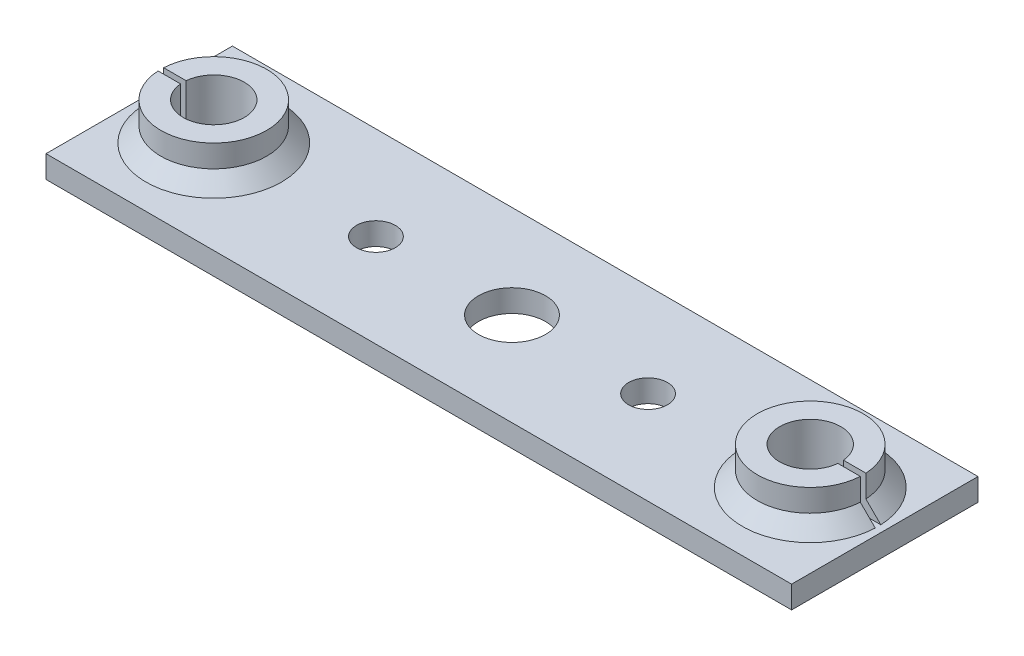
SolidWorks part; units mm, degrees
ref_plane "Front Plane" through (0, 0, 0) normal (0, 0, 1) x (1, 0, 0)
ref_plane "Top Plane" through (0, 0, 0) normal (0, 1, 0) x (1, 0, 0)
ref_plane "Right Plane" through (0, 0, 0) normal (1, 0, 0) x (0, 0, -1)
sketch "Sketch1" plane through (0, 0, 0) normal (0, 1, 0) x (1, 0, 0)
  line L0 (0, 18.2751) -> (0, -23.7638) construction
  line L1 (-40.7915, 0) -> (38.5461, 0) construction
  line L3 (50, -12.5) -> (-50, -12.5)
  line L4 (50, -12.5) -> (50, 12.5)
  line L5 (50, 12.5) -> (-50, 12.5)
  line L6 (-50, -12.5) -> (-50, 12.5)
  line L7 (50, -12.5) -> (-50, 12.5) construction
  line L8 (50, 12.5) -> (-50, -12.5) construction
  circle A0 centre (-40, 0) radius 4.1
  circle A1 centre (40, 0) radius 4.1
  circle A2 centre (-18.25, 0) radius 2.6
  circle A3 centre (18.25, 0) radius 2.6
  circle A4 centre (0, 0) radius 4.5
  point P7 (0, 0)
  dimension "D1" = 8.2
  dimension "D2" = 80
  dimension "D5" = 5.2
  dimension "D6" = 36.5
  dimension "D7" = 9
  dimension "D3" = 25
  dimension "D4" = 100
extrude "Boss-Extrude1" add sketch "Sketch1" along normal blind 3
sketch "Sketch2" plane through (0, 3, 0) normal (0, 1, 0) x (1, 0, 0)
  line L0 (0, 12.5) -> (0, -12.5) construction
  line L1 (50, 12.5) -> (-50, 12.5) construction
  line L2 (-50, -12.5) -> (50, -12.5) construction
  line L3 (-40, 0) -> (-47.1, 0) construction
  line L4 (-44.0828, 0.375) -> (-47.0901, 0.375)
  line L5 (-44.0828, -0.375) -> (-47.0901, -0.375)
  line L6 (44.0828, -0.375) -> (47.0901, -0.375)
  line L7 (44.0828, 0.375) -> (47.0901, 0.375)
  circle A0 centre (-40, 0) radius 4.1
  circle A1 centre (-40, 0) radius 7.1
  circle A2 centre (40, 0) radius 4.1
  circle A3 centre (40, 0) radius 7.1
  circle M6 centre (-40, 0) radius 4.1
  circle M11 centre (40, 0) radius 4.1
  dimension "D1" = 8.2
  dimension "D2" = 3
  dimension "D3" = 0.75
extrude "Boss-Extrude2" add sketch "Sketch2" along normal blind 5 contours L5 A1 L4 M6 | A3 L6 L7 M11 region at (-45.5865, 3, -0.5757) region at (45.5865, 3, 0.5757)
chamfer "Chamfer1" distance 2 angle 45 2 edges at (32.9, 3, 0) (-32.9, 3, 0)
